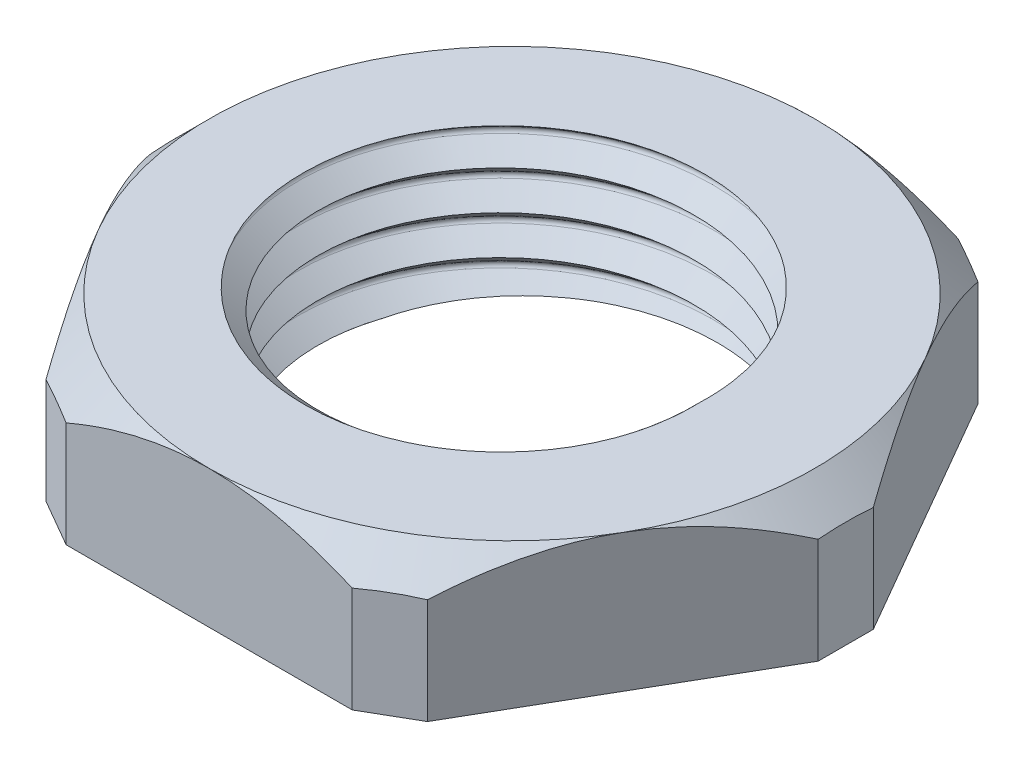
SolidWorks part; units mm, degrees
material "PA Type 6"
ref_plane "Front Plane" through (0, 0, 0) normal (0, 0, 1) x (1, 0, 0)
ref_plane "Top Plane" through (0, 0, 0) normal (0, 1, 0) x (1, 0, 0)
ref_plane "Right Plane" through (0, 0, 0) normal (1, 0, 0) x (0, 0, -1)
ref_axis "Axis1" through (0, 3.0377, 0) along (0, -1, 0)
sketch "ProfileS" plane through (0, 0, 0) normal (0, 1, 0) x (1, 0, 0)
  line L1 (6.3509, -11) -> (12.7017, 0)
  line L2 (12.7017, 0) -> (6.3509, 11)
  line L3 (6.3509, 11) -> (-6.3509, 11)
  line L4 (-6.3509, 11) -> (-12.7017, 0)
  line L5 (-12.7017, 0) -> (-6.3509, -11)
  line L6 (-6.3509, -11) -> (6.3509, -11)
  circle A2 centre (0, 0) radius 11 construction
  dimension "HexWidth" = 22
extrude "Profile" add sketch "ProfileS" along normal mid plane 5
sketch "ThreadOuterDiaRef" plane through (0, 2.5, 0) normal (0, 1, 0) x (1, 0, 0)
  circle A0 centre (0, 0) radius 7.6 construction
  dimension "MajorDia" = 15.2
sketch "LockNutThreadProfile" plane through (0, 0, 0) normal (0, 0, 1) x (1, 0, 0)
  line L0 (-6.8349, 3.2055) -> (-7.5378, 2.6157)
  line L2 (-7.5378, 2.3843) -> (-6.8349, 1.7945)
  line L3 (-6.8349, 1.7945) -> (-6.8349, 3.2055) construction
  line L4 (7.6, 2.5) -> (-7.6, 2.5) construction
  line L8 (-7.5378, 2.3843) -> (-7.6757, 2.5) construction
  line L9 (-7.6757, 2.5) -> (-7.5378, 2.6157) construction
  line L11 (-6.8349, 3.2055) -> (-6.7592, 3.269)
  line L13 (-6.7592, 3.269) -> (-6.7592, 1.731)
  line L14 (-6.7592, 1.731) -> (-6.8349, 1.7945)
  arc A0 (-7.5378, 2.6157) -> (-7.5378, 2.3843) centre (-7.4408, 2.5) ccw
  point P13 (-7.6, 2.5)
  dimension "PitchAngle" = 80
  dimension "HOffset" = 0.0757
  dimension "ThreadCutOffset" = 0.0757
sketch "MinorDiaRef" plane through (0, 2.5, 0) normal (0, 1, 0) x (-1, 0, 0)
  circle A0 centre (0, 0) radius 6.8349
  point P3 (6.8349, 0)
  dimension "Dim" = 13.6698
extrude "ThruHole" cut sketch "MinorDiaRef" against normal through all
sketch "Sketch7" plane through (0, 2.5, 0) normal (0, 1, 0) x (-1, 0, 0)
  circle A0 centre (0, 0) radius 6.8349
  circle A1 centre (0, 0) radius 6.8349 construction
curve "Helix/Spiral1" pitch 1.411 height 5 radius 6.8349 centre (0, 2.5, 0) axis (0, -1, 0) start towards (0, 0, 1) parameters "Pitch"=1.411
sweep "LockNutThread" cut profiles "LockNutThreadProfile" path "Helix/Spiral1" align with end faces yes
sketch "TopChamferS" plane through (0, 2.5, 0) normal (0, 1, 0) x (1, 0, 0)
  line L0 (6.3509, 11) -> (-6.3509, 11) construction
  circle A0 centre (0, 0) radius 11
extrude "TopChamfer" cut sketch "TopChamferS" against normal through all draft 45 flip side to cut
sketch "CornerFlatS" plane through (0, 0, 0) normal (0, 1, 0) x (1, 0, 0)
  line L0 (-5.1962, 11) -> (-6.9282, 10)
  line L1 (0, 11) -> (-6.3509, 11) construction
  line L2 (-6.3509, 11) -> (-9.5263, 5.5) construction
  line L3 (-6.3509, 11) -> (-6.0622, 10.5) construction
  dimension "CornerWidth" = 2
extrude "CornerFlat" cut sketch "CornerFlatS" against normal through all and the other way through all flip side to cut
pattern_circular "CirPattern1" count 6 over 360 about axis through (0, 2.5, 0) along (0, 1, 0) of "CornerFlat"
sketch "EjectionPinHoleS" plane through (0, -2.5, 0) normal (0, -1, 0) x (-1, 0, 0)
  line L0 (3.8, -6.5818) -> (6.0622, -10.5) construction
  line L2 (5.1962, -11) -> (6.9282, -10) construction
  circle A0 centre (4.9311, -8.5409) radius 0.7
  circle A1 centre (0, 0) radius 7.6 construction
  dimension "Dia" = 1.4
extrude "EjectionPinHole" cut sketch "EjectionPinHoleS" against normal blind 1 draft 5
pattern_circular "CirPattern2" count 3 over 360 about axis through (0, 3.0377, 0) along (0, -1, 0) of "EjectionPinHole"
equation "\"Radius@LockNutThreadProfile\"=.107*\"Pitch@LockNutThreadProfile\""
equation "\"HOffset@LockNutThreadProfile\" = .1 * \"Height@LockNutThreadProfile\""
equation "\"D3@Helix/Spiral1\"=\"Height@Profile\""
equation "\"ThreadCutOffset@LockNutThreadProfile\" = \"HOffset@LockNutThreadProfile\""
equation "\"Pitch@Helix/Spiral1\"=\"Pitch@LockNutThreadProfile\""
